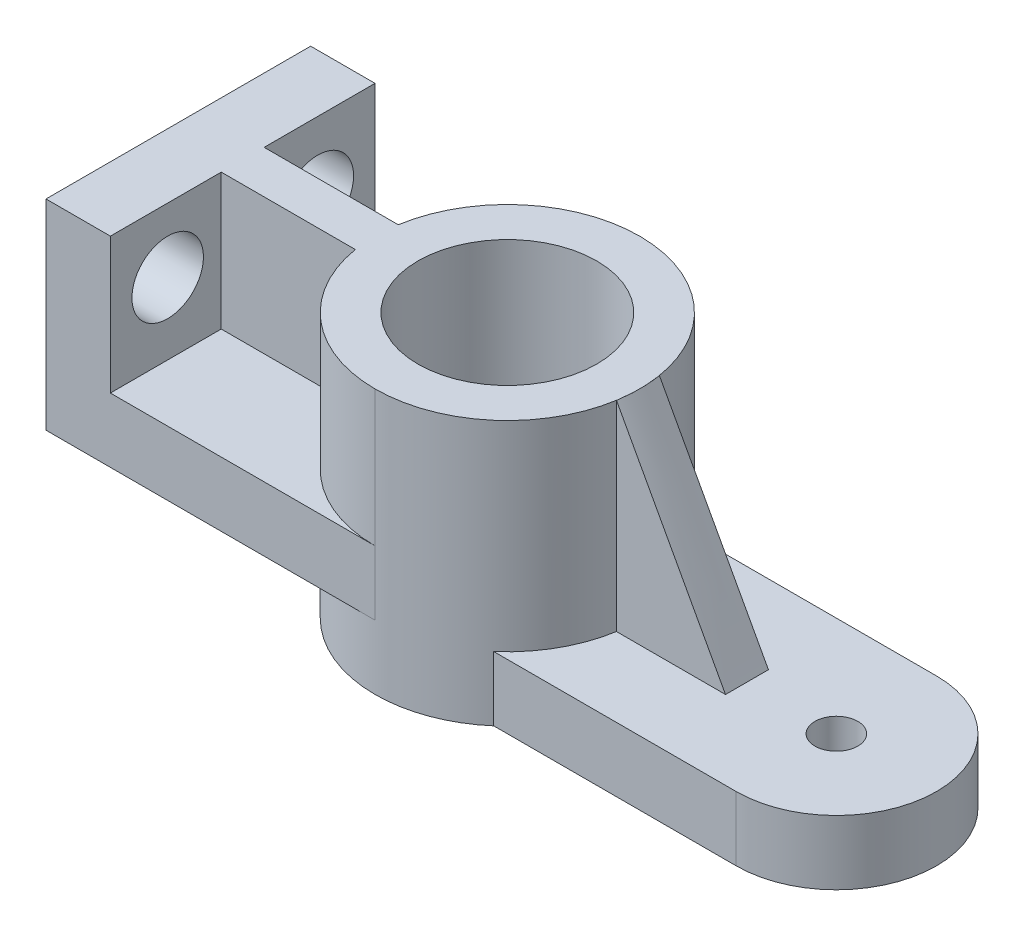
SolidWorks part; units mm, degrees
ref_plane "Front Plane" through (0, 0, 0) normal (0, 0, 1) x (1, 0, 0)
ref_plane "Top Plane" through (0, 0, 0) normal (0, 1, 0) x (1, 0, 0)
ref_plane "Right Plane" through (0, 0, 0) normal (1, 0, 0) x (0, 0, -1)
sketch "Sketch1" plane through (0, 0, 0) normal (0, 1, 0) x (1, 0, 0)
  line L0 (0, 0) -> (-30783.3237, 0) construction
  line L1 (0, 0) -> (0, -30783.3237) construction
  line L2 (-46, 18.5) -> (-46, -18.5)
  line L3 (-37, 18.5) -> (-37, -18.5)
  line L4 (-46, 18.5) -> (-37, 18.5)
  line L5 (-46, -18.5) -> (-37, -18.5)
  line L6 (-37, 18.5) -> (0, 18.5)
  line L7 (-37, -18.5) -> (0, -18.5)
  line L8 (-37, 3) -> (-18.2551, 3)
  line L9 (-37, -3) -> (-18.2551, -3)
  line L10 (46, 14) -> (12.0934, 14)
  line L11 (46, -14) -> (12.0934, -14)
  circle A0 centre (0, 0) radius 12.5
  circle A1 centre (0, 0) radius 18.5
  arc A3 (46, -14) -> (46, 14) centre (46, 0) ccw
  circle A5 centre (46, 0) radius 3
  point P11 (-46, 0)
  dimension "D1" = 25
  dimension "D2" = 37
  dimension "D7" = 6
  dimension "D8" = 28
  dimension "D3" = 46
  dimension "D5" = 37
  dimension "D6" = 6
  dimension "D9" = 46
  dimension "D4" = 9
extrude "Boss-Extrude1" add sketch "Sketch1" along normal blind 28 contours L2 L5 L3 L4 | A1 L8 L3 L9 region at (-41.5, 0, 0) region at (-27.7092, 0, 0)
extrude "Boss-Extrude2" add sketch "Sketch1<3>" along normal blind 9 contours A1 L9 L3 L7 | A1 L6 L3 L8 region at (-25.0257, 0, -11.4939) region at (-25.0257, 0, 11.4939)
sketch "Sketch1<3>" plane through (0, 0, 0) normal (0, 1, 0) x (1, 0, 0) same geometry as "Sketch1"
extrude "Boss-Extrude3" add sketch "Sketch1<4>" along normal blind 28 and the other way blind 9 contours A1 A0 region at (6.2693, 0, -16.8481)
sketch "Sketch1<4>" plane through (0, 0, 0) normal (0, 1, 0) x (1, 0, 0) same geometry as "Sketch1"
extrude "Boss-Extrude4" add sketch "Sketch1<5>" against normal blind 9 contours L11 A3 L10 A1 A5 region at (36.6113, 0, 0)
sketch "Sketch1<5>" plane through (0, 0, 0) normal (0, 1, 0) x (1, 0, 0) same geometry as "Sketch1"
sketch "Sketch3" plane through (0, 28, 0) normal (0, 1, 0) x (1, 0, 0)
  arc A1 (12.0934, -14) -> (12.0934, 14) centre (0, 0) ccw construction
  arc A2 (18.2551, -3) -> (18.2551, 3) centre (0, 0) ccw
sketch "Sketch5" plane through (0, 0, 0) normal (0, 1, 0) x (1, 0, 0)
  line L1 (33.5, -3) -> (33.5, 3)
  arc A1 (18.2551, -3) -> (18.2551, 3) centre (0, 0) ccw construction
  point P9 (33.5, 0)
  dimension "D1" = 33.5
  dimension "D2" = 6
ref_plane "Plane1" through (0, 0, 3) normal (0, 0, -1) x (-1, 0, 0)
sketch "Sketch6" plane through (0, 0, 3) normal (0, 0, -1) x (-1, 0, 0)
  line L0 (-18.2551, 28) -> (-33.5, 0)
ref_plane "Plane2" through (0, 0, -3) normal (0, 0, -1) x (-1, 0, 0)
sketch "Sketch7" plane through (0, 0, -3) normal (0, 0, -1) x (-1, 0, 0)
  line L0 (-18.2551, 28) -> (-33.5, 0)
surface "Surface-Loft1"
surface "Surface-Extrude1" sketch "Sketch7"
hole_wizard "Ø10.0mm Dowel Hole1" positions "3DSketch1" profile "Sketch9" hole size "Ø10.0" standard "ANSI Metric" end condition through all
sketch3d "3DSketch1"
  line L0 (-37, 28, 3) -> (-37, 28, 18.5) construction
  line L1 (-37, 28, -18.5) -> (-37, 9, -18.5) construction
  point P0 (-37, 19, 10.4889)
  point P2 (-37, 18.3166, -10.5)
  dimension "D1" = 21
  dimension "D2" = 9
  dimension "D3" = 8
sketch "Sketch9" plane through (-37, 19, 10.4889) normal (0, 1, 0) x (0, 0, -1)
  line L0 (0, 0) -> (0, 9)
  line L1 (0, 9) -> (5, 9)
  line L2 (5, 9) -> (5, 0)
  line L5 (5, 0) -> (0, 0)
  line L11 (0, -6.35) -> (0, 107.95) construction
  dimension "Thru Hole Dia." = 10
  dimension "Thru Hole Depth" = 9
